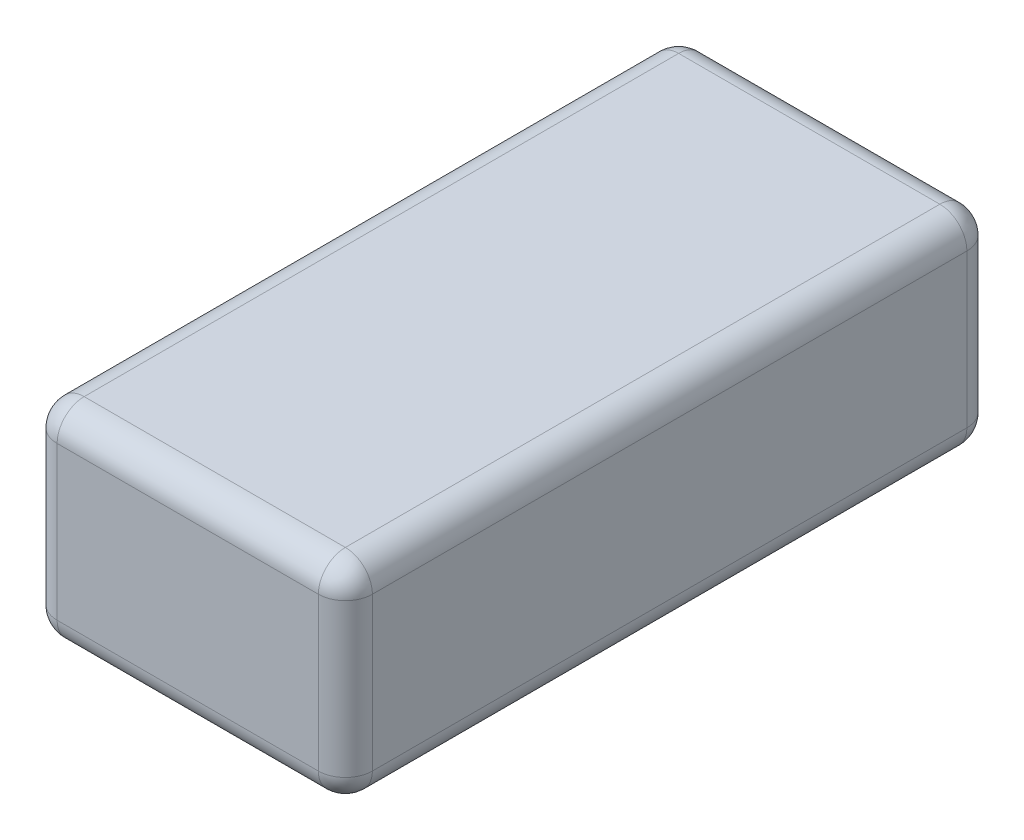
SolidWorks part; units mm, degrees
ref_plane "Front Plane" through (0, 0, 0) normal (0, 0, 1) x (1, 0, 0)
ref_plane "Top Plane" through (0, 0, 0) normal (0, 1, 0) x (1, 0, 0)
ref_plane "Right Plane" through (0, 0, 0) normal (1, 0, 0) x (0, 0, -1)
sketch "Sketch1" plane through (0, 0, 0) normal (0, 1, 0) x (1, 0, 0)
  line L1 (-17.5, 36) -> (17.5, 36)
  line L2 (-17.5, 36) -> (-17.5, -36)
  line L3 (-17.5, -36) -> (17.5, -36)
  line L4 (17.5, 36) -> (17.5, -36)
  line L5 (-17.5, 36) -> (17.5, -36) construction
  line L6 (-17.5, -36) -> (17.5, 36) construction
  point P0 (0, 0)
  dimension "D1" = 72
  dimension "D2" = 35
extrude "Boss-Extrude1" add sketch "Sketch1" along normal blind 23
fillet "Fillet1" radius 3 12 edges at (-17.5, 11.5, -36) (-17.5, 11.5, 36) (17.5, 11.5, 36) (17.5, 11.5, -36) (0, 0, -36) (-17.5, 0, 0) (0, 0, 36) (17.5, 0, 0) (0, 23, 36) (-17.5, 23, 0) (0, 23, -36) (17.5, 23, 0)
